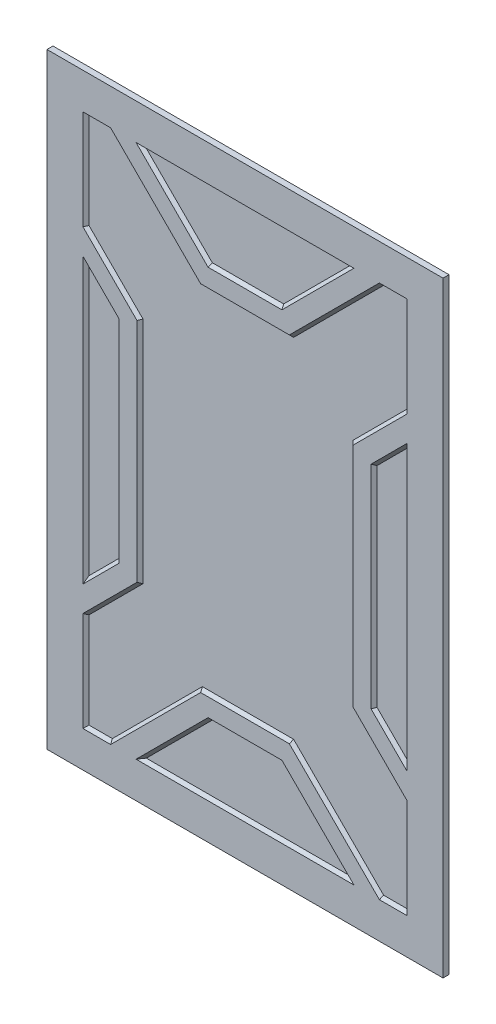
SolidWorks part; units mm, degrees
ref_plane "Plan de face" through (0, 0, 0) normal (0, 0, 1) x (1, 0, 0)
ref_plane "Plan de dessus" through (0, 0, 0) normal (0, 1, 0) x (1, 0, 0)
ref_plane "Plan de droite" through (0, 0, 0) normal (1, 0, 0) x (0, 0, -1)
sketch "Esquisse1" plane through (0, 0, 0) normal (0, 0, 1) x (1, 0, 0)
  line L1 (0, 0) -> (660, 0)
  line L2 (0, 0) -> (0, 1010)
  line L3 (0, 1010) -> (660, 1010)
  line L4 (660, 0) -> (660, 1010)
  dimension "D1" = 1010
  dimension "D2" = 660
extrude "Boss.-Extru.1" add sketch "Esquisse1" along normal blind 10
sketch "Esquisse2" plane through (0, 0, 10) normal (0, 0, 1) x (1, 0, 0)
  line L0 (256.066, 800) -> (150, 693.934) construction
  line L1 (120, 328.4924) -> (120, 681.5076)
  line L2 (120, 681.5076) -> (60, 741.5076)
  line L3 (268.4924, 830) -> (391.5076, 830)
  line L4 (330, 950) -> (330, 60) construction
  line L5 (600, 505) -> (60, 505) construction
  line L6 (60, 950) -> (60, 783.934)
  line L7 (60, 783.934) -> (150, 693.934)
  line L8 (60, 950) -> (60, 60)
  line L9 (60, 60) -> (600, 60)
  line L10 (600, 60) -> (600, 950)
  line L11 (600, 950) -> (60, 950)
  line L12 (60, 950) -> (60, 60) construction
  line L13 (60, 60) -> (600, 60) construction
  line L14 (600, 60) -> (600, 950) construction
  line L15 (600, 950) -> (60, 950) construction
  line L16 (150, 693.934) -> (150, 316.066)
  line L17 (60, 950) -> (106.066, 950)
  line L18 (106.066, 950) -> (256.066, 800)
  line L19 (403.934, 800) -> (256.066, 800)
  line L20 (511.5076, 950) -> (148.4924, 950)
  line L21 (148.4924, 950) -> (268.4924, 830)
  line L22 (510, 693.934) -> (510, 316.066)
  line L23 (60, 741.5076) -> (60, 268.4924)
  line L24 (540, 328.4924) -> (540, 681.5076)
  line L25 (150, 693.934) -> (150, 800) construction
  line L26 (150, 800) -> (256.066, 800) construction
  line L27 (540, 681.5076) -> (600, 741.5076)
  line L28 (600, 741.5076) -> (600, 268.4924)
  line L29 (600, 783.934) -> (510, 693.934)
  line L30 (600, 950) -> (600, 783.934)
  line L31 (600, 950) -> (553.934, 950)
  line L32 (553.934, 950) -> (403.934, 800)
  line L33 (511.5076, 950) -> (391.5076, 830)
  line L34 (120, 328.4924) -> (60, 268.4924)
  line L35 (60, 226.066) -> (150, 316.066)
  line L36 (600, 60) -> (553.934, 60)
  line L37 (600, 60) -> (600, 226.066)
  line L38 (60, 60) -> (60, 226.066)
  line L39 (60, 60) -> (106.066, 60)
  line L40 (511.5076, 60) -> (148.4924, 60)
  line L41 (268.4924, 180) -> (391.5076, 180)
  line L42 (403.934, 210) -> (256.066, 210)
  line L43 (148.4924, 60) -> (268.4924, 180)
  line L44 (106.066, 60) -> (256.066, 210)
  line L45 (511.5076, 60) -> (391.5076, 180)
  line L46 (553.934, 60) -> (403.934, 210)
  line L47 (600, 226.066) -> (510, 316.066)
  line L48 (540, 328.4924) -> (600, 268.4924)
  point P20 (330, 800)
  point P23 (510, 505)
  point P31 (330, 830)
  point P33 (120, 505)
  point P34 (150, 505)
  point P47 (540, 505)
  dimension "D2" = 90
  dimension "D3" = 150
  dimension "D4" = 150
  dimension "D5" = 45
  dimension "D6" = 30
  dimension "D7" = 30
  dimension "D8" = 30
  dimension "D9" = 30
  dimension "D1" = 60
extrude "Enlèv. mat.-Extru.1" cut sketch "Esquisse2" against normal blind 5
chamfer "Chanfrein1" distance 5 angle 45 36 edges at (330, 60, 5) (208.4924, 120, 5) (330, 180, 5) (451.5076, 120, 5) (60, 505, 5) (90, 711.5076, 5) (120, 505, 5) (90, 298.4924, 5) (600, 505, 5) (570, 298.4924, 5) (540, 505, 5) (570, 711.5076, 5) (181.066, 875, 5) (330, 800, 5) (478.934, 875, 5) (576.967, 950, 5) (600, 866.967, 5) (555, 738.934, 5) (510, 505, 5) (555, 271.066, 5) (600, 143.033, 5) (576.967, 60, 5) (478.934, 135, 5) (330, 210, 5) (181.066, 135, 5) (83.033, 60, 5) (60, 143.033, 5) (105, 271.066, 5) (150, 505, 5) (105, 738.934, 5) (60, 866.967, 5) (83.033, 950, 5) (330, 950, 5) (451.5076, 890, 5) (330, 830, 5) (208.4924, 890, 5)
